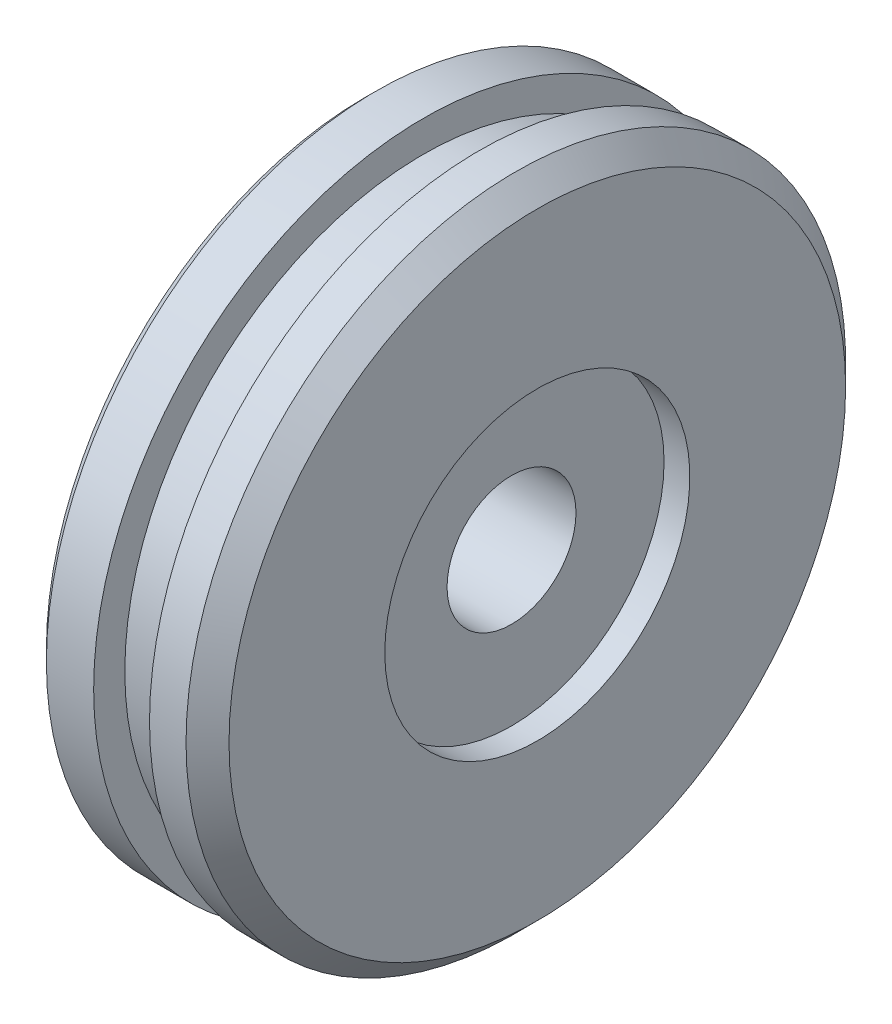
SolidWorks part; units mm, degrees
ref_plane "Front Plane" through (0, 0, 0) normal (0, 0, 1) x (1, 0, 0)
ref_plane "Top Plane" through (0, 0, 0) normal (0, 1, 0) x (1, 0, 0)
ref_plane "Right Plane" through (0, 0, 0) normal (1, 0, 0) x (0, 0, -1)
ref_plane "Plane1" through (0, 0, -52) normal (0, 0, 1) x (1, 0, 0)
sketch "Sketch1" plane through (0, 0, -52) normal (0, 0, 1) x (1, 0, 0)
  line L0 (72.2, -65) -> (90.2, -65) construction
  line L1 (77.2, -65) -> (85.2, -65)
  line L2 (85.2, -65) -> (85.2, -50.65)
  line L3 (85.2, -50.65) -> (84.2, -49.65)
  line L4 (84.2, -49.65) -> (77.7, -49.65)
  line L5 (77.7, -49.65) -> (77.2, -50.15)
  line L6 (77.2, -50.15) -> (77.2, -65)
revolve "Revolve1" add sketch "Sketch1" angle 360 about L0
sketch "Sketch2" plane through (0, 0, -52) normal (0, 0, 1) x (1, 0, 0)
  line L0 (74.9, -65) -> (87.5, -65) construction
  line L1 (79.9, -51.1) -> (82.5, -51.1)
  line L2 (82.5, -51.1) -> (82.5, -48.65)
  line L3 (82.5, -48.65) -> (79.9, -48.65)
  line L4 (79.9, -48.65) -> (79.9, -51.1)
revolve "Revolve2" add sketch "Sketch2" angle 360 about L0
combine bodies "Combine1" operation type subtract main body 101 bodies to subtract 102
sketch "Sketch3" plane through (0, 0, 0) normal (0, 0, 1) x (1, 0, 0)
  line L1 (76.7, -76.5) -> (79, -76.5)
  line L2 (76.7, -76.5) -> (76.7, -53.5)
  line L3 (76.7, -53.5) -> (79, -53.5)
  line L4 (79, -76.5) -> (79, -53.5)
extrude "Boss-Extrude1" add sketch "Sketch3" along normal blind 6.6 from offset 55.3 separate body offset against normal yes
combine bodies "Combine2" operation type subtract main body 103 bodies to subtract 104
sketch "Sketch4" plane through (0, 0, 0) normal (0, 0, 1) x (1, 0, 0)
  line L1 (76.7, -68.3) -> (79, -68.3)
  line L2 (76.7, -68.3) -> (76.7, -61.7)
  line L3 (76.7, -61.7) -> (79, -61.7)
  line L4 (79, -68.3) -> (79, -61.7)
extrude "Boss-Extrude2" add sketch "Sketch4" along normal blind 23 from offset 63.5 separate body offset against normal yes
combine bodies "Combine3" operation type subtract main body 105 bodies to subtract 106
sketch "Sketch5" plane through (0, 0, 0) normal (1, 0, 0) x (0, 0, -1)
  circle A0 centre (52, -65) radius 4.6
extrude "Boss-Extrude3" add sketch "Sketch5" along normal blind 2.3 from offset 76.7 separate body
combine bodies "Combine4" operation type subtract main body 107 bodies to subtract 108
sketch "Sketch6" plane through (0, 0, 0) normal (1, 0, 0) x (0, 0, -1)
  circle A0 centre (52, -65) radius 7.1
extrude "Boss-Extrude4" add sketch "Sketch6" along normal blind 1.7 from offset 84 separate body
combine bodies "Combine5" operation type subtract main body 109 bodies to subtract 110
sketch "Sketch7" plane through (0, 0, 0) normal (1, 0, 0) x (0, 0, -1)
  circle A0 centre (52, -65) radius 3
extrude "Boss-Extrude5" add sketch "Sketch7" along normal blind 5.2 from offset 78.9 separate body
combine bodies "Combine6" operation type subtract main body 111 bodies to subtract 112
sketch "Sketch8" plane through (0, 0, 0) normal (0, 0, 1) x (1, 0, 0)
  line L1 (78.9, -59.5) -> (83, -59.5)
  line L2 (78.9, -59.5) -> (78.9, -57.4)
  line L3 (78.9, -57.4) -> (83, -57.4)
  line L4 (83, -59.5) -> (83, -57.4)
extrude "Boss-Extrude6" add sketch "Sketch8" along normal blind 1.8 from offset 52.9 separate body offset against normal yes
combine bodies "Combine7" operation type subtract main body 113 bodies to subtract 114
sketch "Sketch9" plane through (0, 0, 0) normal (0, 0, 1) x (1, 0, 0)
  line L1 (78.9, -65.9) -> (83, -65.9)
  line L2 (78.9, -65.9) -> (78.9, -64.1)
  line L3 (78.9, -64.1) -> (83, -64.1)
  line L4 (83, -65.9) -> (83, -64.1)
extrude "Boss-Extrude7" add sketch "Sketch9" along normal blind 2.1 from offset 46.5 separate body offset against normal yes
combine bodies "Combine8" operation type subtract main body 115 bodies to subtract 116
sketch "Sketch10" plane through (0, 0, 0) normal (0, 0, 1) x (1, 0, 0)
  line L1 (78.9, -72.6) -> (83, -72.6)
  line L2 (78.9, -72.6) -> (78.9, -70.5)
  line L3 (78.9, -70.5) -> (83, -70.5)
  line L4 (83, -72.6) -> (83, -70.5)
extrude "Boss-Extrude8" add sketch "Sketch10" along normal blind 1.8 from offset 52.9 separate body offset against normal yes
combine bodies "Combine9" operation type subtract main body 117 bodies to subtract 118
sketch "Sketch11" plane through (0, 0, 0) normal (0, 0, 1) x (1, 0, 0)
  line L1 (78.9, -65.9) -> (83, -65.9)
  line L2 (78.9, -65.9) -> (78.9, -64.1)
  line L3 (78.9, -64.1) -> (83, -64.1)
  line L4 (83, -65.9) -> (83, -64.1)
extrude "Boss-Extrude9" add sketch "Sketch11" along normal blind 2.1 from offset 59.6 separate body offset against normal yes
combine bodies "Combine10" operation type subtract main body 119 bodies to subtract 120
sketch "Sketch12" plane through (0, 0, 0) normal (0, 0, 1) x (1, 0, 0)
  line L1 (78.9, -57.4) -> (84.2, -57.4)
  line L2 (78.9, -57.4) -> (78.9, -55)
  line L3 (78.9, -55) -> (84.2, -55)
  line L4 (84.2, -57.4) -> (84.2, -55)
extrude "Boss-Extrude10" add sketch "Sketch12" along normal blind 1.8 from offset 52.9 separate body offset against normal yes
combine bodies "Combine11" operation type subtract main body 121 bodies to subtract 122
sketch "Sketch13" plane through (0, 0, 0) normal (0, 0, 1) x (1, 0, 0)
  line L1 (78.9, -65.9) -> (84.2, -65.9)
  line L2 (78.9, -65.9) -> (78.9, -64.1)
  line L3 (78.9, -64.1) -> (84.2, -64.1)
  line L4 (84.2, -65.9) -> (84.2, -64.1)
extrude "Boss-Extrude11" add sketch "Sketch13" along normal blind 2.4 from offset 44.4 separate body offset against normal yes
combine bodies "Combine12" operation type subtract main body 123 bodies to subtract 124
sketch "Sketch14" plane through (0, 0, 0) normal (0, 0, 1) x (1, 0, 0)
  line L1 (78.9, -75) -> (84.2, -75)
  line L2 (78.9, -75) -> (78.9, -72.6)
  line L3 (78.9, -72.6) -> (84.2, -72.6)
  line L4 (84.2, -75) -> (84.2, -72.6)
extrude "Boss-Extrude12" add sketch "Sketch14" along normal blind 1.8 from offset 52.9 separate body offset against normal yes
combine bodies "Combine13" operation type subtract main body 125 bodies to subtract 126
sketch "Sketch15" plane through (0, 0, 0) normal (0, 0, 1) x (1, 0, 0)
  line L1 (78.9, -65.9) -> (84.2, -65.9)
  line L2 (78.9, -65.9) -> (78.9, -64.1)
  line L3 (78.9, -64.1) -> (84.2, -64.1)
  line L4 (84.2, -65.9) -> (84.2, -64.1)
extrude "Boss-Extrude13" add sketch "Sketch15" along normal blind 2.4 from offset 62 separate body offset against normal yes
combine bodies "Combine14" operation type subtract main body 127 bodies to subtract 128
